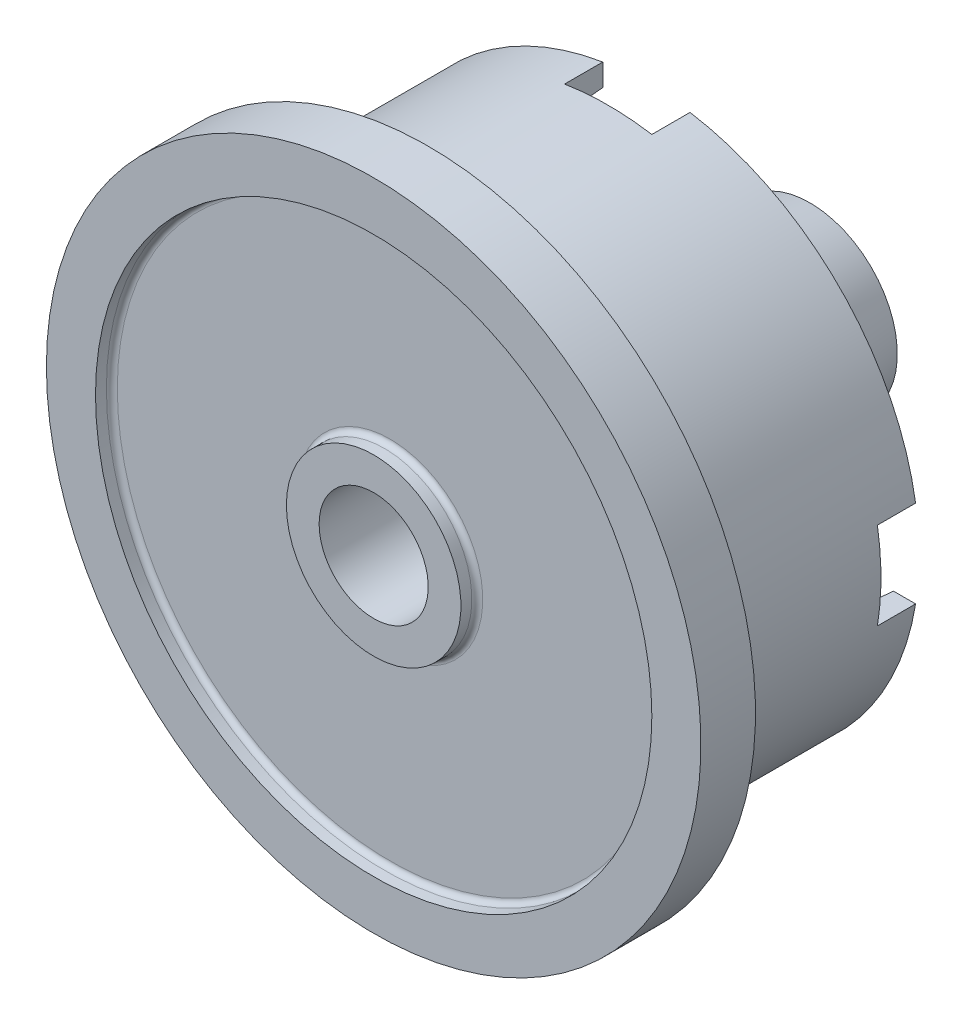
SolidWorks part; units mm, degrees
other "DetailItem1"
ref_plane "Front Plane" through (0, 0, 0) normal (0, 0, 1) x (1, 0, 0)
ref_plane "Top Plane" through (0, 0, 0) normal (0, 1, 0) x (1, 0, 0)
ref_plane "Right Plane" through (0, 0, 0) normal (1, 0, 0) x (0, 0, -1)
sketch "Sketch2" plane through (0, 0, 0) normal (0, 1, 0) x (1, 0, 0)
  line L0 (-50, -80) -> (-50, -70)
  line L1 (-50, -70) -> (-40, -70)
  line L2 (-40, -70) -> (-40, -30)
  line L3 (-40, -30) -> (-36, -30)
  line L4 (-36, -30) -> (-32, -70)
  line L5 (-32, -70) -> (-16, -70)
  line L6 (-16, -70) -> (-6, 0)
  line L7 (0, 0) -> (-6, 0)
  line L8 (-50, -80) -> (-41, -80)
  line L9 (-41, -80) -> (-41, -78)
  line L10 (-40, -77) -> (-7, -77)
  line L11 (-6, -78) -> (-6, -80)
  line L12 (-6, -80) -> (0, -80)
  line L14 (10, 0) -> (10, -80) construction
  line L15 (0, 0) -> (0, -20)
  line L16 (0, -20) -> (-2, -20)
  line L19 (0, -60) -> (0, -80)
  line L20 (0, -60) -> (-2, -60)
  line L21 (-2, -60) -> (-2, -20)
  arc A0 (-40, -77) -> (-41, -78) centre (-40, -78) ccw
  arc A1 (-6, -78) -> (-7, -77) centre (-7, -78) ccw
  dimension "D18" = 2
  dimension "D19" = 2
  dimension "D2" = 20
  dimension "D3" = 24
  dimension "D4" = 32
  dimension "D5" = 20
  dimension "D6" = 20
  dimension "D7" = 10
  dimension "D8" = 80
  dimension "D9" = 100
  dimension "D10" = 7
  dimension "D11" = 52
  dimension "D12" = 84
  dimension "D13" = 92
  dimension "D14" = 120
  dimension "D15" = 102
  dimension "D16" = 40
  dimension "D20" = 32
revolve "Revolve1" add sketch "Sketch2" angle 360 about L14
sketch "Sketch3" plane through (0, 0, 30) normal (0, 0, -1) x (-1, 0, 0)
  line L0 (-10, -60) -> (-10, 60) construction
  line L1 (50, 0) -> (-70, 0) construction
  line L2 (39.3559, -8) -> (31.2311, -8)
  line L3 (39.5663, 8) -> (31.2311, 8)
  circle A2 centre (-10, 0) radius 50 construction
  arc A3 (39.3559, -8) -> (39.3559, 8) centre (-10, 0) ccw
  circle A4 centre (-10, 0) radius 60 construction
  arc A5 (31.2311, -8) -> (31.2311, 8) centre (-10, 0) ccw
  circle M3 centre (-10, 0) radius 50
  circle M4 centre (-10, 0) radius 46
  dimension "D3" = 42
  dimension "D1" = 8
  dimension "D2" = 16
extrude "Cut-Extrude2" cut sketch "Sketch3" against normal blind 7 contours L3 L2 M3 M4 | A5 L2 L3 M4 region at (-37.7756, 0, 30) region at (-33.7547, 0, 30)
pattern_circular "CirPattern1" count 4 over 360 about axis through (10, 0, 30) along (0, 0, -1) of "Cut-Extrude2"
sketch "Sketch4" [suppressed] plane through (0, 0, 0) normal (0, 0, -1) x (-1, 0, 0)
  line L1 (-10, 0) -> (-85.8899, 0)
  line L2 (-10, 0) -> (-10, 70.8063)
  line L3 (-10, 70.8063) -> (-85.8899, 70.8063)
  line L4 (-85.8899, 0) -> (-85.8899, 70.8063)
  line L5 (-10, 0) -> (-82.3165, 0)
  line L6 (-10, 0) -> (-10, -72.7943)
  line L7 (-10, -72.7943) -> (-82.3165, -72.7943)
  line L8 (-82.3165, 0) -> (-82.3165, -72.7943)
  circle M5 centre (-10, 0) radius 16
extrude "Cut-Extrude3" [suppressed] cut sketch "Sketch4" against normal through all both and the other way through all contours L1 L4 L3 L2 M5 | L8 L5 L1 L6 L7 M5 | L6 L5 L8 L7 | L2 L1 L4 L3
